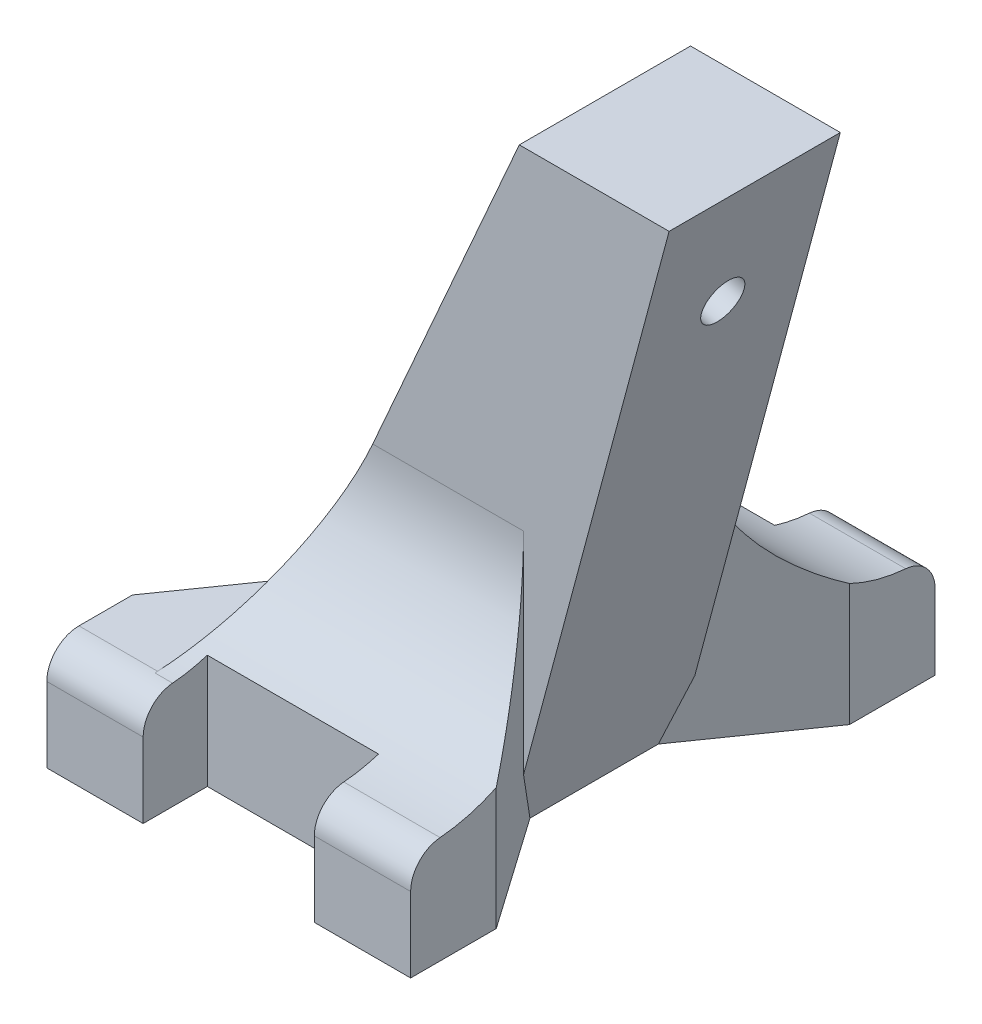
SolidWorks part; units mm, degrees
ref_plane "Alzado" through (0, 0, 0) normal (0, 0, 1) x (1, 0, 0)
ref_plane "Planta" through (0, 0, 0) normal (0, 1, 0) x (1, 0, 0)
ref_plane "Vista lateral" through (0, 0, 0) normal (1, 0, 0) x (0, 0, -1)
sketch "Croquis1" plane through (0, 0, 0) normal (0, 1, 0) x (1, 0, 0)
  line L0 (0, 22.0375) -> (0, -21.3925) construction
  line L1 (8, 18.51) -> (-8, 18.51)
  line L2 (-8, 18.51) -> (-8, 24.51)
  line L3 (-8, 24.51) -> (-17, 24.51)
  line L4 (-17, 24.51) -> (-17, 16.51)
  line L5 (-17, 16.51) -> (-9.6408, 6)
  line L6 (-9.6408, 6) -> (-9.6408, -6)
  line L7 (-9.6408, 0) -> (9.6408, 0) construction
  line L8 (-17, -16.51) -> (-9.6408, -6)
  line L9 (-17, -24.51) -> (-17, -16.51)
  line L10 (-8, -24.51) -> (-17, -24.51)
  line L11 (-8, -18.51) -> (-8, -24.51)
  line L12 (8, -18.51) -> (-8, -18.51)
  line L13 (8, -18.51) -> (8, -24.51)
  line L14 (8, -24.51) -> (17, -24.51)
  line L15 (17, -24.51) -> (17, -16.51)
  line L16 (17, -16.51) -> (9.6408, -6)
  line L17 (9.6408, 6) -> (9.6408, -6)
  line L18 (17, 16.51) -> (9.6408, 6)
  line L19 (17, 24.51) -> (17, 16.51)
  line L20 (8, 24.51) -> (17, 24.51)
  line L21 (8, 18.51) -> (8, 24.51)
  line L23 (-9.6408, 6) -> (-14.2408, 6)
  line L24 (-9.6408, 6) -> (-9.6408, -6)
  line L25 (-9.6408, -6) -> (-14.2408, -6)
  line L26 (-14.2408, 6) -> (-14.2408, -6)
  point P18 (0, 0)
  point P19 (0, -18.51)
  point P28 (0, 18.51)
  dimension "D1" = 24.51
  dimension "D2" = 8
  dimension "D3" = 6
  dimension "D4" = 9
  dimension "D5" = 8
  dimension "D6" = 6
  dimension "D7" = 145
  dimension "D8" = 4.6
extrude "Saliente-Extruir1" add sketch "Croquis1" along normal blind 10 contours L21 L1 L2 L3 L4 L5 L6 L8 L9 L10 L11 L12 L13 L14 L15 L16 L17 L18 L19 L20
fillet "Redondeo1" radius 3 4 edges at (-12.5, 10, -24.51) (12.5, 10, -24.51) (12.5, 10, 24.51) (-12.5, 10, 24.51)
sketch "Croquis4" plane through (0, 0, 0) normal (0, 0, 1) x (1, 0, 0)
  line L8 (24.646, 56) -> (9.6408, 0)
  line L9 (9.6408, 0) -> (28.1624, 0)
  line L10 (24.646, 56) -> (10.646, 56)
  line L11 (10.646, 56) -> (-9.6408, 10)
  line L12 (-9.6408, 10) -> (-9.6408, 0)
  line L13 (-9.6408, 0) -> (9.6408, 0)
  dimension "D1" = 75
  dimension "D2" = 14
extrude "Saliente-Extruir2" add sketch "Croquis4" along normal mid plane 16
fillet "Redondeo2" radius 15 2 edges at (0.7002, 10, 8) (0.7002, 10, -8)
sketch "Croquis6" plane through (8.995, -2.4102, 0) normal (0.9659, -0.2588, 0) x (0, 0, -1)
  line L1 (-8, 60.4707) -> (8, 60.4707) construction
  circle A0 centre (0, 48.9307) radius 2
  dimension "D1" = 4
  dimension "D2" = 11.54
extrude "Cortar-Extruir1" cut sketch "Croquis6" against normal through all contours A0
sketch "Croquis7" plane through (-11.7631, 5.1877, 0) normal (-0.915, 0.4035, 0) x (0, 0, 1)
  circle A0 centre (0, 47.5235) radius 3.5
  circle A1 centre (0, 47.5235) radius 2.0238
  dimension "D1" = 7
extrude "Saliente-Extruir4" add sketch "Croquis7" along normal blind 1
